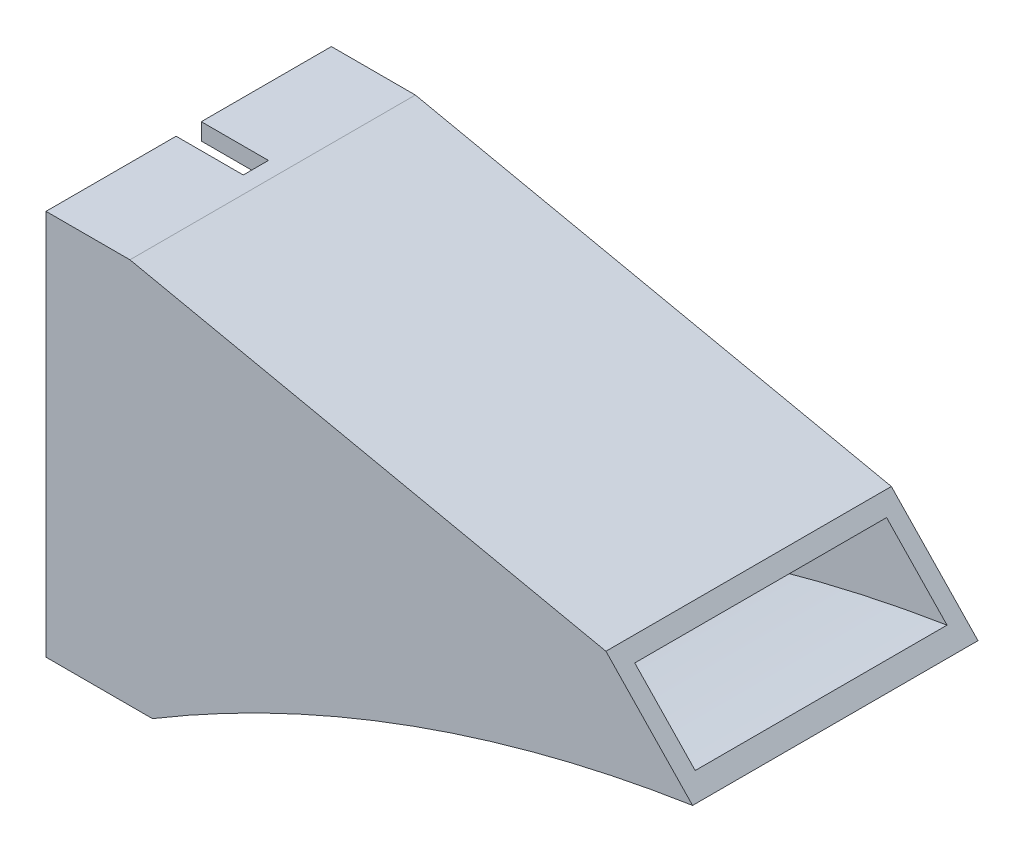
SolidWorks part; units mm, degrees
ref_plane "Front Plane" through (0, 0, 0) normal (0, 0, 1) x (1, 0, 0)
ref_plane "Top Plane" through (0, 0, 0) normal (0, 1, 0) x (1, 0, 0)
ref_plane "Right Plane" through (0, 0, 0) normal (1, 0, 0) x (0, 0, -1)
sketch "Sketch1" plane through (0, 0, 0) normal (0, 0, 1) x (1, 0, 0)
  line L0 (22.4, 5.7) -> (22.4, 28.7)
  line L1 (22.4, 28.7) -> (27.4, 28.7)
  line L2 (27.4, 28.7) -> (55.753, 22.6836)
  line L3 (55.753, 22.6836) -> (60.9146, 17.3096)
  line L4 (22.4, 5.7) -> (28.7393, 5.7)
  line L5 (85.4488, 17.4701) -> (83.6998, 17.8412) construction
  line L6 (83.6998, 17.8412) -> (-21.7307, 40.213) construction
  arc A0 (60.9146, 17.3096) -> (28.7393, 5.7) centre (74.3215, -70.2378) ccw
  dimension "D7" = 88.568
  dimension "D1" = 5
  dimension "D2" = 6.3393
  dimension "D3" = 23
  dimension "D4" = 38.5146
  dimension "D5" = 33.353
  dimension "D6" = 5.3741
  dimension "D8" = 22.4
  dimension "D9" = 5.7
extrude "Boss-Extrude3" add sketch "Sketch1" against normal blind 17 from offset 1
sketch "Sketch2" plane through (0, 0, 1) normal (0, 0, 1) x (1, 0, 0)
  line L0 (22.4, 6.7) -> (28.463, 6.7)
  line L2 (22.4, 6.7) -> (22.4, 27.7)
  line L3 (22.4, 27.7) -> (27.2951, 27.7)
  line L4 (60.0699, 18.1891) -> (56.4693, 21.9379)
  line L5 (60.9146, 17.3096) -> (55.753, 22.6836) construction
  line L6 (56.4693, 21.9379) -> (54.4498, 21.9379)
  line L7 (24.4, 27.7) -> (-0.0106, 27.7) construction
  line L9 (22.4, 28.7) -> (22.4, 5.7) construction
  line L10 (54.4498, 21.9379) -> (27.2951, 27.7)
  line L11 (55.753, 22.6836) -> (27.4, 28.7) construction
  line L12 (22.4, 5.7) -> (28.7393, 5.7) construction
  arc A0 (60.0699, 18.1891) -> (28.463, 6.7) centre (74.3215, -70.2378) ccw
  arc A3 (60.9146, 17.3096) -> (28.7393, 5.7) centre (74.3215, -70.2378) ccw construction
  dimension "D4" = 1
  dimension "D1" = 0
  dimension "D2" = 1
  dimension "D3" = 1
  dimension "D5" = 0.7457
extrude "Cut-Extrude1" cut sketch "Sketch2" against normal blind 15 from offset 1 offset against normal yes
sketch "Sketch3" plane through (22.4, 0, 0) normal (-1, 0, 0) x (0, 0, 1)
  line L0 (-16, 28.7) -> (1, 28.7) construction
  line L1 (-8.25, 30.2529) -> (-6.75, 30.2529)
  line L2 (-8.25, 30.2529) -> (-8.25, 27.1471)
  line L3 (-8.25, 27.1471) -> (-6.75, 27.1471)
  line L4 (-6.75, 30.2529) -> (-6.75, 27.1471)
  line L5 (-8.25, 30.2529) -> (-6.75, 27.1471) construction
  line L6 (-8.25, 27.1471) -> (-6.75, 30.2529) construction
  point P0 (-7.5, 28.7)
  dimension "D1" = 1.5
extrude "Cut-Extrude2" cut sketch "Sketch3" against normal blind 4
